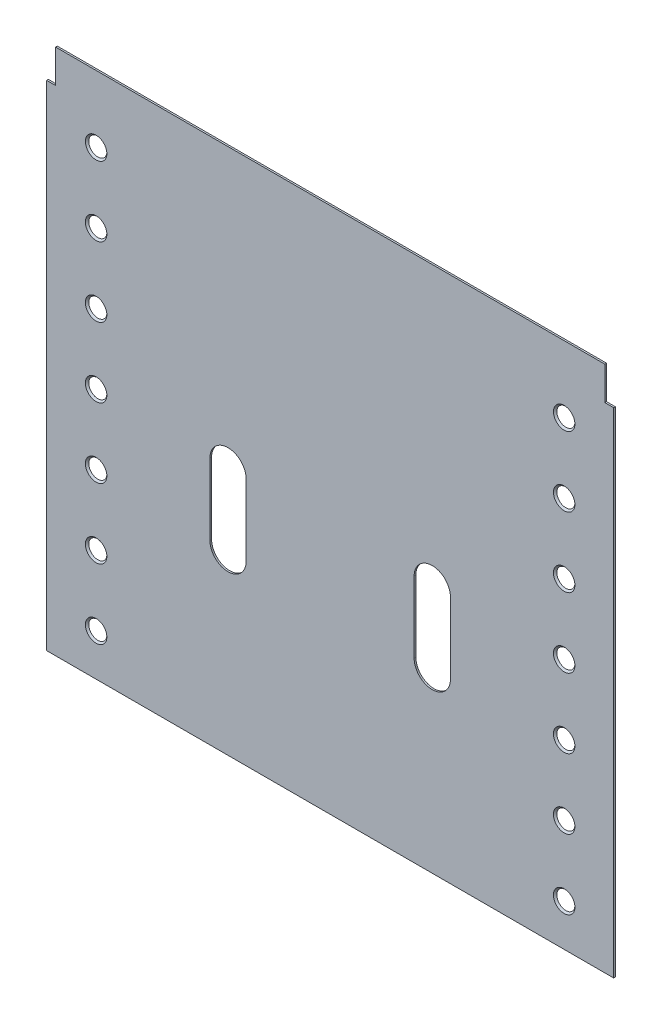
SolidWorks part; units mm, degrees
ref_plane "Front Plane" through (0, 0, 0) normal (0, 0, 1) x (1, 0, 0)
ref_plane "Top Plane" through (0, 0, 0) normal (0, 1, 0) x (1, 0, 0)
ref_plane "Right Plane" through (0, 0, 0) normal (1, 0, 0) x (0, 0, -1)
sketch "Sketch1" plane through (0, 0, 0) normal (0, 0, -1) x (1, 0, 0)
  line L1 (-203.2, 237) -> (0, 237)
  line L2 (-203.2, 237) -> (-203.2, 60)
  line L3 (-203.2, 60) -> (0, 60)
  line L4 (0, 237) -> (0, 60)
  dimension "D2" = 203.2
  dimension "D3" = 177
extrude "Boss-Extrude1" add sketch "Sketch1" along normal blind 0.6096
sketch "Sketch2" plane through (0, 0, -0.6096) normal (0, 0, -1) x (1, 0, 0)
  line L0 (-138.2, 180) -> (-138.2, 141.5) construction
  line L1 (0, 237) -> (-203.2, 237) construction
  line L2 (-138.2, 180) -> (-138.2, 237) construction
  line L3 (-138.2, 173.5) -> (-138.2, 148) construction
  line L6 (-131.7, 173.5) -> (-131.7, 148)
  line L7 (-144.7, 173.5) -> (-144.7, 148)
  line L8 (-138.2, 160.75) -> (-203.2, 160.75) construction
  line L9 (-203.2, 237) -> (-203.2, 60) construction
  line L10 (-65, 180) -> (-65, 141.5) construction
  line L11 (-65, 180) -> (-65, 237) construction
  line L12 (-65, 173.5) -> (-65, 148) construction
  line L16 (-58.5, 173.5) -> (-58.5, 148)
  line L17 (-71.5, 173.5) -> (-71.5, 148)
  line L18 (-65, 160.75) -> (0, 160.75) construction
  line L19 (0, 60) -> (0, 237) construction
  arc A2 (-131.7, 173.5) -> (-144.7, 173.5) centre (-138.2, 173.5) ccw
  arc A3 (-144.7, 148) -> (-131.7, 148) centre (-138.2, 148) ccw
  arc A6 (-58.5, 173.5) -> (-71.5, 173.5) centre (-65, 173.5) ccw
  arc A7 (-71.5, 148) -> (-58.5, 148) centre (-65, 148) ccw
  point P5 (-138.2, 160.75)
  point P18 (-65, 160.75)
  dimension "D4" = 6.5
  dimension "D6" = 57
  dimension "D5" = 6.5
  dimension "D1" = 65
  dimension "D2" = 57
  dimension "D3" = 38.5
  dimension "D7" = 65
  dimension "D8" = 38.5
extrude "Cut-Extrude7" cut sketch "Sketch2" against normal through all
ref_plane "Plane1" through (-101.6, 0, 0) normal (1, 0, 0) x (0, 0, -1)
sketch "Sketch4" plane through (0, 0, 0) normal (0, 0, 1) x (1, 0, 0)
  line L0 (-203.2, -60) -> (0, -60) construction
  line L1 (-3.175, -60) -> (-200.025, -60)
  line L2 (-3.175, -60) -> (-3.175, -60.6096)
  line L3 (-3.175, -60.6096) -> (-200.025, -60.6096)
  line L4 (-200.025, -60) -> (-200.025, -60.6096)
  line L5 (-3.175, -237) -> (-3.175, 2) construction
  line L6 (-200.025, 2) -> (-200.025, -237) construction
  dimension "D1" = 0.6096
extrude "Boss-Extrude2" add sketch "Sketch4" along normal blind 12
sketch "Sketch8" plane through (0, 0, -0.6096) normal (0, 0, -1) x (-1, 0, 0)
  circle A0 centre (185.47, -222) radius 3.75
  circle A1 centre (185.47, -197) radius 3.75
  circle A2 centre (185.47, -172) radius 3.75
  circle A3 centre (185.47, -147) radius 3.75
  circle A4 centre (185.47, -122) radius 3.75
  circle A5 centre (185.47, -97) radius 3.75
  dimension "D1" = 7.5
sketch "Sketch13" plane through (0, 0, 12) normal (0, 0, 1) x (1, 0, 0)
  line L1 (-3.175, -60.6096) -> (-200.025, -60.6096)
  line L2 (-3.175, -60.6096) -> (-3.175, -60)
  line L3 (-3.175, -60) -> (-200.025, -60)
  line L4 (-200.025, -60.6096) -> (-200.025, -60)
sketch "Sketch14" plane through (0, 0, 0) normal (0, 0, 1) x (1, 0, 0)
  line L1 (-3.175, -60) -> (-200.025, -60)
  line L2 (-3.175, -60) -> (-3.175, -48.062)
  line L3 (-3.175, -48.062) -> (-200.025, -48.062)
  line L4 (-200.025, -60) -> (-200.025, -48.062)
  dimension "D1" = 11.938
extrude "Boss-Extrude3" add sketch "Sketch14" against normal up to surface (0.6096 mm away) up to face at (-138.2, -160.75, -0.6096)
extrude "Cut-Extrude9" cut sketch "Sketch13" against normal up to surface (12 mm away) up to face at (-65, -160.75, 0)
hole_wizard "CSK for M3 Flat Head Machine Screw3" positions "Sketch15" profile "Sketch16" countersink size "M3" standard "ANSI Metric" end condition through all
sketch "Sketch15" plane through (0, 0, 0) normal (0, 0, 1) x (1, 0, 0)
  point P0 (-185.47, -222)
  point P3 (-185.47, -197)
  point P6 (-185.47, -172)
  point P9 (-185.47, -147)
  point P12 (-185.47, -122)
  point P15 (-185.47, -97)
  point P18 (-185.47, -72)
sketch "Sketch16" plane through (-185.47, -222, 0) normal (1, 0, 0) x (0, -1, 0)
  line L0 (0, 0) -> (0, 0.6096)
  line L1 (0, 0.6096) -> (1.7, 0.6096)
  line L2 (1.7, 0.6096) -> (1.7, 2.15)
  line L3 (1.7, 2.15) -> (3.85, 0)
  line L5 (3.85, 0) -> (0, 0)
  line L6 (-1.7, 2.15) -> (-3.85, 0) construction
  line L11 (0, -6.35) -> (0, 107.95) construction
  dimension "Thru Hole Dia." = 3.4
  dimension "Thru Hole Depth" = 0.6096
  dimension "Near C'Sink Dia." = 7.7
  dimension "Near C'Sink Angle" = 90
ref_plane "Plane2" through (-101.6, 0, 0) normal (-1, 0, 0) x (0, 0, 1)
mirror "Mirror1" about plane through (-101.6, 0, 0) normal (-1, 0, 0) of "CSK for M3 Flat Head Machine Screw3"
